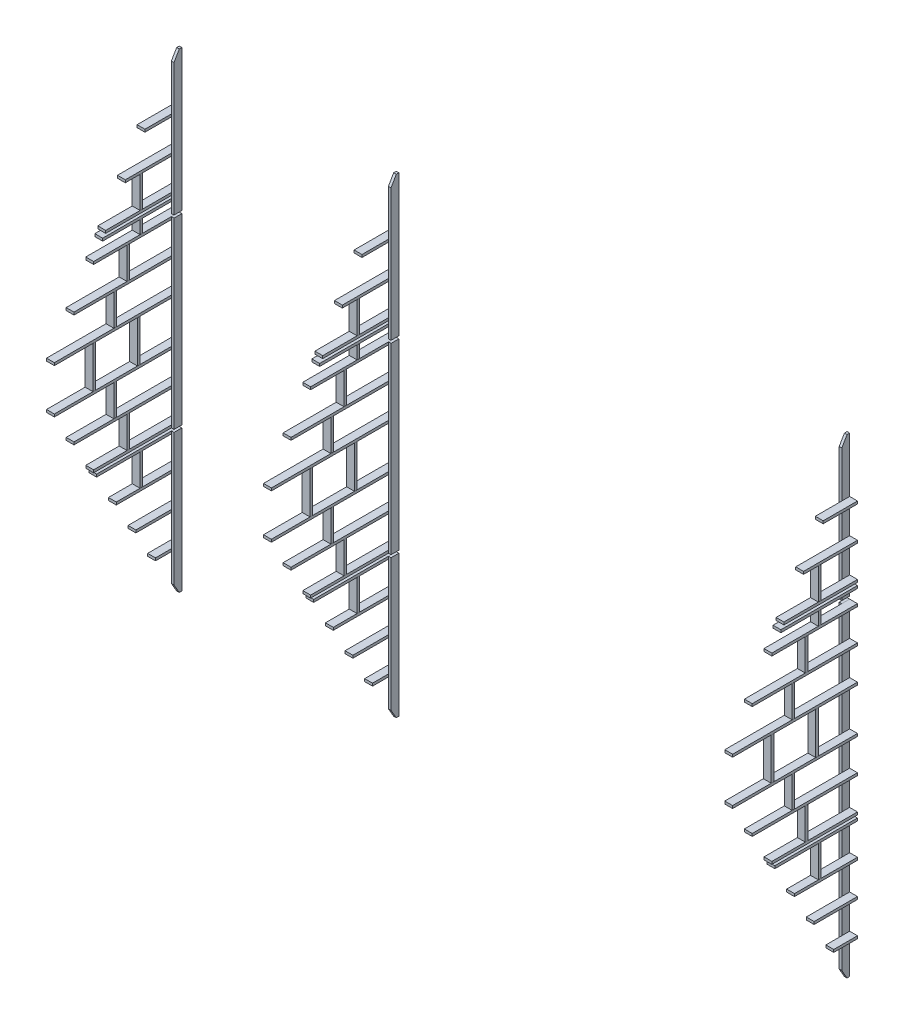
SolidWorks part; units mm, degrees
ref_plane "Спереди" through (0, 0, 0) normal (0, 0, 1) x (1, 0, 0)
ref_plane "Сверху" through (0, 0, 0) normal (0, 1, 0) x (1, 0, 0)
ref_plane "Справа" through (0, 0, 0) normal (1, 0, 0) x (0, 0, -1)
other "Configuration Table"
sketch "Эскиз2" plane through (-110, 0, 0) normal (-1, 0, 0) x (0, 0, 1)
  line L0 (-50, 0) -> (-50, 6600) construction
  line L1 (-50, 2700) -> (1529.9782, 2700)
  line L2 (-50, 2700) -> (-50, 2650)
  line L3 (-50, 2650) -> (1529.9782, 2650)
  line L4 (1529.9782, 2700) -> (1529.9782, 2650)
  line L5 (-50, 4100) -> (2338.2686, 4100)
  line L6 (-50, 4100) -> (-50, 4050)
  line L7 (-50, 4050) -> (2338.2686, 4050)
  line L8 (2338.2686, 4100) -> (2338.2686, 4050)
  line L9 (2651.9993, 4500) -> (-50, 4500) construction
  line L10 (-50, 8900) -> (-50, 100) construction
  line L11 (0, 0) -> (2598.0762, 4500) construction
  line L12 (2651.9993, 4500) -> (53.923, 0) construction
  line L13 (0, 9000) -> (2598.0762, 4500) construction
  line L14 (1550, 4100) -> (750, 4100) construction
  line L15 (-50, 4900) -> (-50, 4950)
  line L16 (-50, 4900) -> (2338.2686, 4900)
  line L17 (2338.2686, 4900) -> (2338.2686, 4950)
  line L18 (-50, 4950) -> (2338.2686, 4950)
  line L19 (1550, 4100) -> (1550, 4900) construction
  line L28 (1550, 4899) -> (1600, 4899)
  line L29 (1550, 4899) -> (1550, 4101)
  line L30 (1550, 4101) -> (1600, 4101)
  line L31 (1600, 4899) -> (1600, 4101)
  line L32 (750, 4100) -> (750, 4900) construction
  line L33 (750, 4899) -> (700, 4899)
  line L34 (750, 4899) -> (750, 4101)
  line L35 (750, 4101) -> (700, 4101)
  line L36 (700, 4899) -> (700, 4101)
  line L38 (1962.9909, 3400) -> (-50, 3400)
  line L39 (1962.9909, 3400) -> (1962.9909, 3450)
  line L40 (1962.9909, 3450) -> (-50, 3450)
  line L41 (-50, 3400) -> (-50, 3450)
  line L43 (-50, 2800) -> (1587.7132, 2800)
  line L44 (-50, 2800) -> (-50, 2750)
  line L45 (-50, 2750) -> (1587.7132, 2750)
  line L46 (1587.7132, 2800) -> (1587.7132, 2750)
  line L47 (1154.7005, 2000) -> (-50, 2000)
  line L48 (1154.7005, 2000) -> (1154.7005, 2050)
  line L49 (1154.7005, 2050) -> (-50, 2050)
  line L50 (-50, 2000) -> (-50, 2050)
  line L51 (779.4229, 1350) -> (-50, 1350)
  line L52 (779.4229, 1350) -> (779.4229, 1400)
  line L53 (779.4229, 1400) -> (-50, 1400)
  line L54 (-50, 1350) -> (-50, 1400)
  line L55 (404.1452, 700) -> (-50, 700)
  line L56 (404.1452, 700) -> (404.1452, 750)
  line L57 (404.1452, 750) -> (-50, 750)
  line L58 (-50, 700) -> (-50, 750)
  line L59 (1200, 4049) -> (1150, 4049)
  line L60 (1200, 4049) -> (1200, 3451)
  line L61 (1200, 3451) -> (1150, 3451)
  line L62 (1150, 4049) -> (1150, 3451)
  line L63 (950, 3399) -> (900, 3399)
  line L64 (950, 3399) -> (950, 2801)
  line L65 (950, 2801) -> (900, 2801)
  line L66 (900, 3399) -> (900, 2801)
  line L67 (700, 2649) -> (650, 2649)
  line L68 (700, 2649) -> (700, 2051)
  line L69 (700, 2051) -> (650, 2051)
  line L70 (650, 2649) -> (650, 2051)
  line L71 (1200, 4951) -> (1150, 4951)
  line L80 (900, 5601) -> (900, 6199)
  line L81 (950, 6199) -> (900, 6199)
  line L82 (950, 5601) -> (950, 6199)
  line L83 (950, 5601) -> (900, 5601)
  line L84 (1150, 4951) -> (1150, 5549)
  line L85 (1200, 5549) -> (1150, 5549)
  line L86 (1200, 4951) -> (1200, 5549)
  line L95 (1587.7132, 6200) -> (1587.7132, 6250)
  line L96 (-50, 6250) -> (1587.7132, 6250)
  line L97 (-50, 6200) -> (-50, 6250)
  line L98 (-50, 6200) -> (1587.7132, 6200)
  line L99 (-50, 5600) -> (-50, 5550)
  line L100 (1962.9909, 5550) -> (-50, 5550)
  line L101 (1962.9909, 5600) -> (1962.9909, 5550)
  line L102 (1962.9909, 5600) -> (-50, 5600)
  line L107 (-50, 4500) -> (-50, 9000) construction
  line L108 (-50, 9000) -> (0, 9000) construction
  line L110 (-50, 6550) -> (1414.5082, 6550)
  line L111 (-50, 6550) -> (-50, 6500)
  line L112 (-50, 6500) -> (1414.5082, 6500)
  line L113 (1414.5082, 6550) -> (1414.5082, 6500)
  line L114 (-50, 6600) -> (1356.7731, 6600)
  line L115 (-50, 6600) -> (-50, 6650)
  line L116 (-50, 6650) -> (1356.7731, 6650)
  line L117 (1356.7731, 6600) -> (1356.7731, 6650)
  line L118 (-50, 7300) -> (981.4955, 7300)
  line L119 (-50, 7300) -> (-50, 7250)
  line L120 (-50, 7250) -> (981.4955, 7250)
  line L121 (981.4955, 7300) -> (981.4955, 7250)
  line L122 (650, 6499) -> (700, 6499)
  line L123 (650, 6499) -> (650, 6251)
  line L124 (650, 6251) -> (700, 6251)
  line L125 (700, 6499) -> (700, 6251)
  line L126 (650, 7249) -> (700, 7249)
  line L127 (650, 7249) -> (650, 6651)
  line L128 (650, 6651) -> (700, 6651)
  line L129 (700, 7249) -> (700, 6651)
  line L130 (-50, 7950) -> (606.2178, 7950)
  line L131 (-50, 7950) -> (-50, 7900)
  line L132 (-50, 7900) -> (606.2178, 7900)
  line L133 (606.2178, 7950) -> (606.2178, 7900)
  point P117 (0, 0)
  dimension "D1" = 50
  dimension "D2" = 800
  dimension "D3" = 1
  dimension "D4" = 1
  dimension "D5" = 600
  dimension "D6" = 600
  dimension "D7" = 600
  dimension "D8" = 600
  dimension "D9" = 600
  dimension "D10" = 1
  dimension "D11" = 1
  dimension "D12" = 400
  dimension "D13" = 1
  dimension "D14" = 1
  dimension "D15" = 200
  dimension "D16" = 200
  dimension "D17" = 1
  dimension "D18" = 1
  dimension "D19" = 200
  dimension "D20" = 600
  dimension "D21" = 1
  dimension "D22" = 1
  dimension "D23" = 600
ref_plane "Плоскость1" through (-8980, 0, 0) normal (1, 0, 0) x (0, 0, -1)
ref_plane "Плоскость2" through (-13130, 0, 0) normal (1, 0, 0) x (0, 0, -1)
extrude "Бобышка-Вытянуть1" add sketch "Эскиз2" along normal blind 50 and the other way blind 100
extrude "Бобышка-Вытянуть2" add sketch "Эскиз2<2>" against normal blind 150 from surface separate body starting at plane "Плоскость1"
sketch "Эскиз2<2>" plane through (-110, 0, 0) normal (-1, 0, 0) x (0, 0, 1) same geometry as "Эскиз2"
extrude "Бобышка-Вытянуть3" add sketch "Эскиз2<3>" against normal blind 150 from surface separate body starting at plane "Плоскость2"
sketch "Эскиз2<3>" plane through (-110, 0, 0) normal (-1, 0, 0) x (0, 0, 1) same geometry as "Эскиз2"
sketch "Эскиз3" plane through (-160, 0, 0) normal (-1, 0, 0) x (0, 0, 1)
  line L0 (0, 0) -> (100, 173.2051)
  line L1 (-50, 2700) -> (100, 2700)
  line L2 (-50, 2700) -> (-50, 0)
  line L3 (-50, 0) -> (0, 0)
  line L4 (100, 2700) -> (100, 173.2051)
  line L5 (0, 0) -> (2598.0762, 4500) construction
  line L6 (-50, 6250) -> (1587.7132, 6250) construction
  line L7 (-50, 2750) -> (100, 2750)
  line L8 (-50, 2750) -> (-50, 6250)
  line L9 (-50, 6250) -> (100, 6250)
  line L10 (100, 2750) -> (100, 6250)
  line L12 (2598.0762, 4500) -> (-50, 4500) construction
  line L13 (-50, 6300) -> (100, 6300)
  line L14 (100, 6300) -> (100, 8826.7949)
  line L15 (0, 9000) -> (100, 8826.7949)
  line L16 (-50, 9000) -> (0, 9000)
  line L17 (-50, 6300) -> (-50, 9000)
  dimension "D1" = 150
extrude "Бобышка-Вытянуть4" add sketch "Эскиз3" along normal blind 50 separate body
extrude "Бобышка-Вытянуть5" add sketch "Эскиз3<2>" against normal blind 50 from surface separate body starting at face at (-8830, 6950, 675)
sketch "Эскиз3<2>" plane through (-160, 0, 0) normal (-1, 0, 0) x (0, 0, 1) same geometry as "Эскиз3"
extrude "Бобышка-Вытянуть6" add sketch "Эскиз3<3>" against normal blind 50 from surface separate body starting at face at (-12980, 7275, 465.7477)
sketch "Эскиз3<3>" plane through (-160, 0, 0) normal (-1, 0, 0) x (0, 0, 1) same geometry as "Эскиз3"
